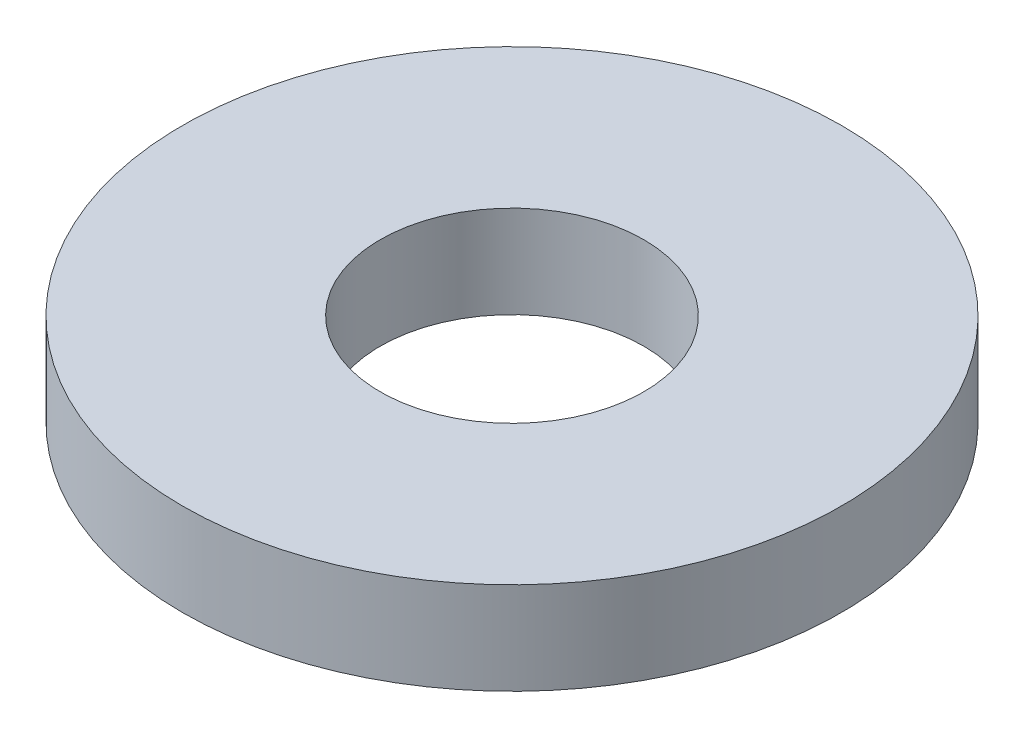
SolidWorks part; units mm, degrees
ref_plane "Front Plane" through (0, 0, 0) normal (0, 0, 1) x (1, 0, 0)
ref_plane "Top Plane" through (0, 0, 0) normal (0, 1, 0) x (1, 0, 0)
ref_plane "Right Plane" through (0, 0, 0) normal (1, 0, 0) x (0, 0, -1)
sketch "Sketch1" plane through (0, 0, 0) normal (0, 1, 0) x (1, 0, 0)
  circle A0 centre (0, 0) radius 75
  dimension "FLANGE_OD" = 150
extrude "Boss-Extrude1" add sketch "Sketch1" along normal blind 21
sketch "Sketch2" plane through (0, 0, 0) normal (0, 1, 0) x (1, 0, 0)
  circle A0 centre (0, 0) radius 30
  dimension "BORE_D" = 60
extrude "Cut-Extrude1" cut sketch "Sketch2" along normal through all
sketch "Sketch3" plane through (0, 21, 0) normal (0, 1, 0) x (1, 0, 0)
  circle A0 centre (0, 0) radius 18.8583 construction
  circle A1 centre (-18.8583, 0) radius 4.1847
  dimension "BOLT_D" = 8.3695
  dimension "BOLT_PCD" = 37.7165
extrude "Cut-Extrude2" cut sketch "Sketch3" against normal blind 18.6594 rebuild error yes
pattern_circular "CirPattern1" count 3 over 360 rebuild error yes
